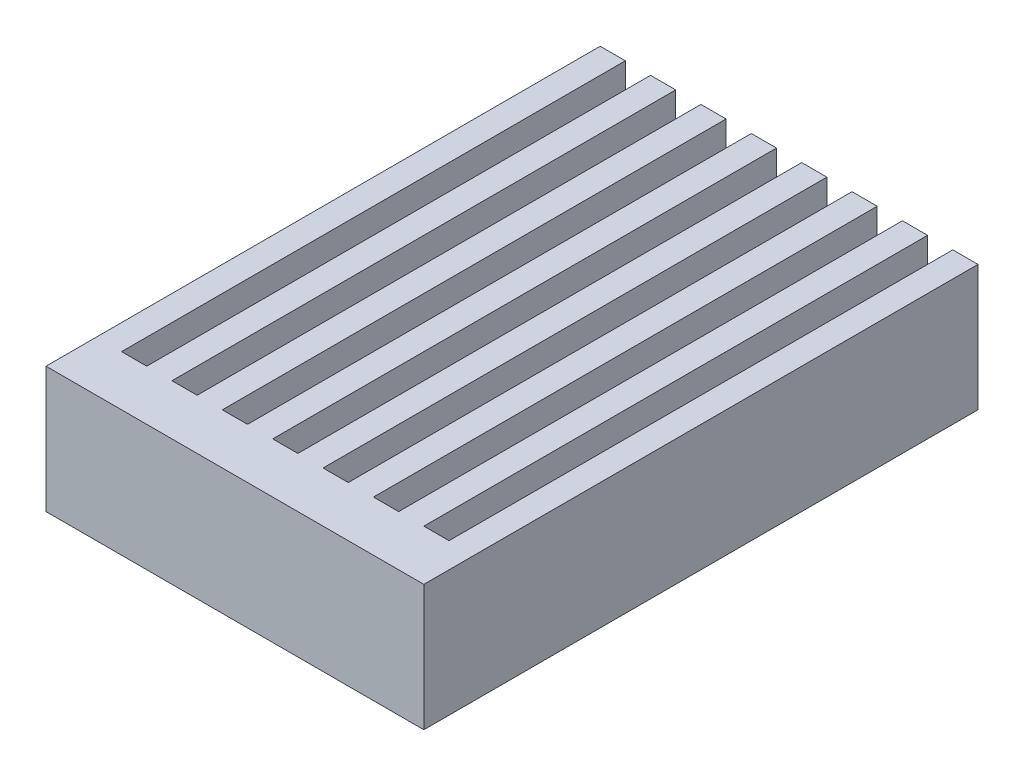
SolidWorks part; units mm, degrees
material "6061 Alloy"
ref_plane "Front Plane" through (0, 0, 0) normal (0, 0, 1) x (1, 0, 0)
ref_plane "Top Plane" through (0, 0, 0) normal (0, 1, 0) x (1, 0, 0)
ref_plane "Right Plane" through (0, 0, 0) normal (1, 0, 0) x (0, 0, -1)
sketch "Sketch1" plane through (0, 0, 0) normal (0, 1, 0) x (1, 0, 0)
  line L1 (-5.6933, -2.3133) -> (9.3067, -2.3133)
  line L2 (-5.6933, -2.3133) -> (-5.6933, -0.3133)
  line L3 (-5.6933, -0.3133) -> (9.3067, -0.3133)
  line L4 (9.3067, -2.3133) -> (9.3067, -0.3133)
  line L5 (-5.6933, -0.3133) -> (-4.6933, -0.3133)
  line L6 (-5.6933, -0.3133) -> (-5.6933, 19.6867)
  line L7 (-5.6933, 19.6867) -> (-4.6933, 19.6867)
  line L8 (-4.6933, -0.3133) -> (-4.6933, 19.6867)
  dimension "D1" = 15
  dimension "D2" = 2
  dimension "D3" = 20
  dimension "D4" = 1
extrude "Boss-Extrude1" add sketch "Sketch1" along normal blind 5 contours L3 L4 L1 L2
extrude "Boss-Extrude2" add sketch "Sketch1<3>" along normal blind 5 contours L6 L7 L8 L5
sketch "Sketch1<3>" plane through (0, 0, 0) normal (0, 1, 0) x (1, 0, 0) same geometry as "Sketch1"
pattern_linear "LPattern1" count 8 spacing 2 along (1, 0, 0) of "Boss-Extrude2"
